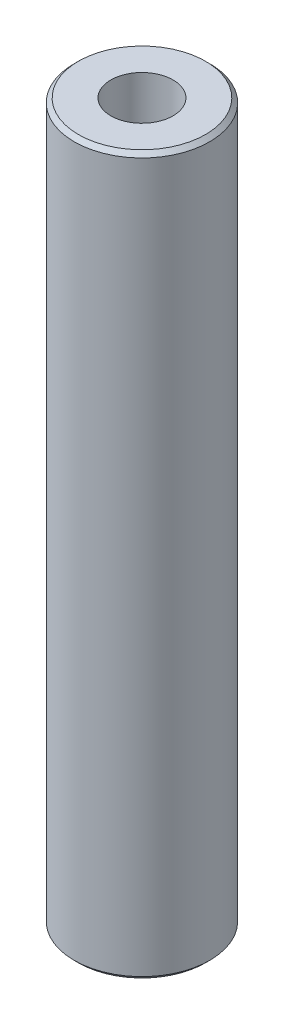
SolidWorks part; units mm, degrees
ref_plane "Front Plane" through (0, 0, 0) normal (0, 0, 1) x (1, 0, 0)
ref_plane "Top Plane" through (0, 0, 0) normal (0, 1, 0) x (1, 0, 0)
ref_plane "Right Plane" through (0, 0, 0) normal (1, 0, 0) x (0, 0, -1)
sketch "Sketch1" plane through (0, 0, 0) normal (0, 1, 0) x (1, 0, 0)
  circle A0 centre (0, 0) radius 55
  dimension "SHAFT_OD" = 110
extrude "Boss-Extrude1" add sketch "Sketch1" along normal blind 582.5531
sketch "Sketch2" plane through (0, 0, 0) normal (0, 1, 0) x (1, 0, 0)
  circle A0 centre (0, 0) radius 25.2843
  dimension "BORE_D" = 50.5687
extrude "Cut-Extrude1" cut sketch "Sketch2" along normal through all
chamfer "Chamfer1" distance 3.394 angle 45 2 edges at (0, 582.5531, 55) (0, 0, 55)
